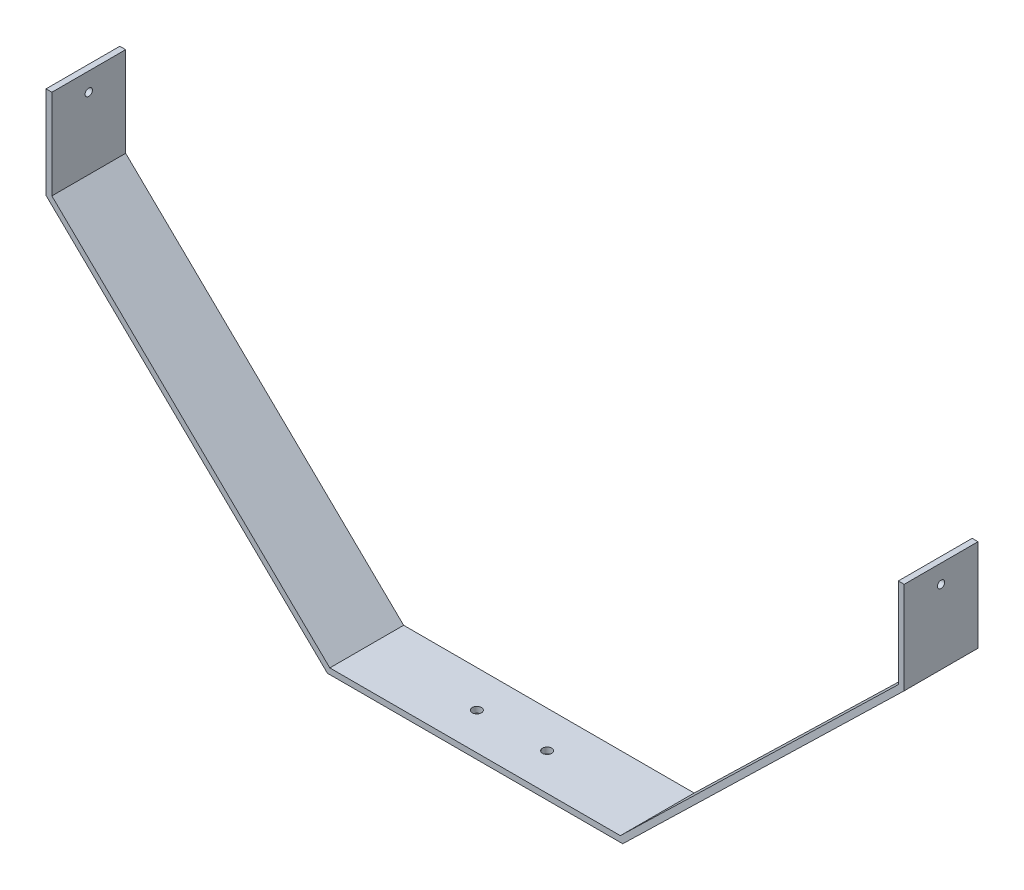
SolidWorks part; units mm, degrees
ref_plane "Front Plane" through (0, 0, 0) normal (0, 0, 1) x (1, 0, 0)
ref_plane "Top Plane" through (0, 0, 0) normal (0, 1, 0) x (1, 0, 0)
ref_plane "Right Plane" through (0, 0, 0) normal (1, 0, 0) x (0, 0, -1)
sketch "Sketch1" plane through (0, 0, 0) normal (0, 0, 1) x (1, 0, 0)
  line L0 (-80, 0) -> (80, 0)
  line L1 (80, 0) -> (232.5, 148)
  line L2 (232.5, 148) -> (232.5, 198)
  line L3 (-80, 0) -> (-232.5, 148)
  line L4 (-232.5, 148) -> (-232.5, 198)
  line L5 (-232.5, 148) -> (232.5, 148) construction
  line L6 (-232.5, 198) -> (232.5, 198) construction
  line L7 (229.325, 149.3431) -> (229.325, 198)
  line L8 (78.7126, 3.175) -> (229.325, 149.3431)
  line L9 (-78.7126, 3.175) -> (78.7126, 3.175)
  line L10 (-78.7126, 3.175) -> (-229.325, 149.3431)
  line L11 (-229.325, 149.3431) -> (-229.325, 198)
  line L12 (-232.5, 198) -> (-229.325, 198)
  line L13 (229.325, 198) -> (232.5, 198)
  point P8 (0, 0)
  dimension "D1" = 160
  dimension "D2" = 465
  dimension "D3" = 198
  dimension "D4" = 50
  dimension "D5" = 3.175
extrude "Boss-Extrude1" add sketch "Sketch1" along normal blind 40
sketch "Sketch3" plane through (0, 3.175, 0) normal (0, 1, 0) x (1, 0, 0)
  line L0 (-78.7126, -20) -> (-19.05, -20) construction
  line L1 (-78.7126, -40) -> (-78.7126, 0) construction
  line L2 (-19.05, -20) -> (19.05, -20) construction
  line L3 (19.05, -20) -> (78.7126, -20) construction
  line L4 (78.7126, -40) -> (78.7126, 0) construction
  circle A0 centre (-19.05, -20) radius 2.5
  circle A1 centre (19.05, -20) radius 2.5
  dimension "D2" = 5
  dimension "D1" = 38.1
extrude "Cut-Extrude1" cut sketch "Sketch3" against normal through all both and the other way through all
sketch "Sketch4" plane through (-232.5, 0, 0) normal (-1, 0, 0) x (0, 0, 1)
  line L0 (20, 198) -> (20, 148) construction
  line L1 (40, 198) -> (0, 198) construction
  line L2 (40, 148) -> (0, 148) construction
  line L3 (0, 188) -> (40, 188) construction
  line L4 (0, 148) -> (0, 198) construction
  line L5 (40, 148) -> (40, 198) construction
  circle A0 centre (20, 188) radius 1.9844
  dimension "D2" = 3.9688
  dimension "D1" = 10
extrude "Cut-Extrude2" cut sketch "Sketch4" against normal through all both
